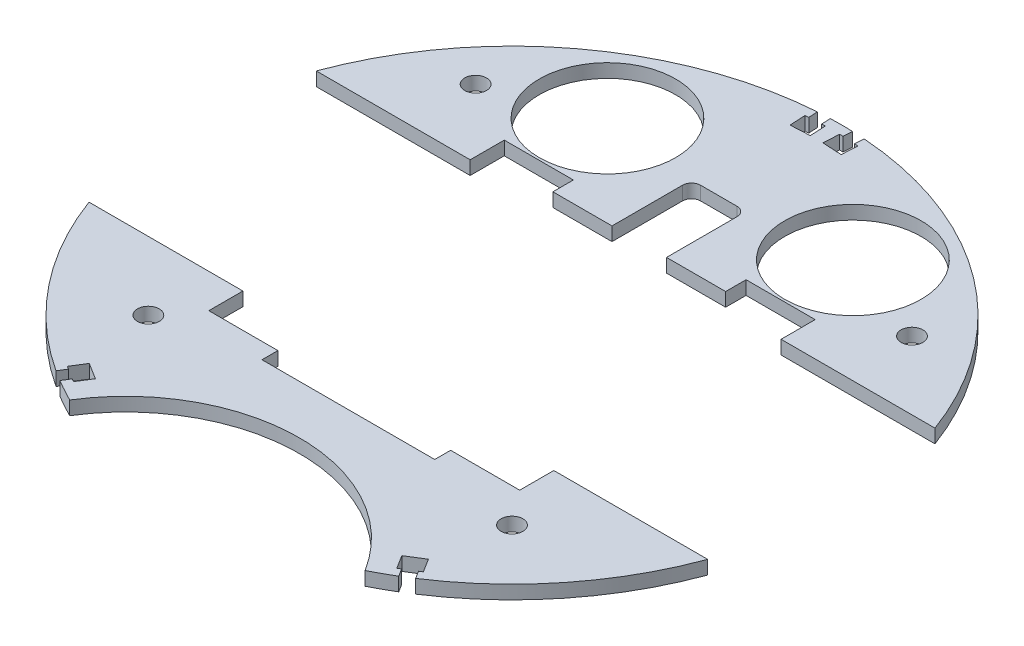
SolidWorks part; units mm, degrees
material "Acrylic (Medium-high impact)"
ref_plane "Front Plane" through (0, 0, 0) normal (0, 0, 1) x (1, 0, 0)
ref_plane "Top Plane" through (0, 0, 0) normal (0, 1, 0) x (1, 0, 0)
ref_plane "Right Plane" through (0, 0, 0) normal (1, 0, 0) x (0, 0, -1)
sketch "Sketch1" plane through (0, 0, 0) normal (0, 1, 0) x (1, 0, 0)
  line L0 (0, -85) -> (-32.4891, -64.8129) construction
  line L1 (0, -85) -> (0, 0) construction
  arc A0 (32.4891, -64.8129) -> (-32.4891, -64.8129) centre (0, 0) ccw
  arc A1 (32.4891, -64.8129) -> (-32.4891, -64.8129) centre (0, -85) ccw
  dimension "D1" = 145
  dimension "D2" = 76.5
  dimension "D3" = 85
extrude "Boss-Extrude1" add sketch "Sketch1" along normal blind 3
sketch "solenoid placement" plane through (0, 3, 0) normal (0, 1, 0) x (1, 0, 0)
  line L4 (-19, -36) -> (19, -36)
  line L5 (-19, 28) -> (-19, -36)
  line L10 (19, 28) -> (-19, 28)
  line L11 (19, -36) -> (19, 28)
  line L12 (-19, -36) -> (19, -36)
  line L13 (-19, 28) -> (-19, -36)
  line L14 (19, 28) -> (-19, 28)
  line L15 (19, -36) -> (19, 28)
  dimension "D1" = 0
extrude "Cut-Extrude1" cut sketch "solenoid placement" against normal through all
sketch "Sketch7" plane through (0, 3, 0) normal (0, 1, 0) x (1, 0, 0)
  circle A3 centre (27, 48) radius 15
  circle A4 centre (27, 48) radius 15
  circle A5 centre (-27, 48) radius 15
  circle A6 centre (-27, 48) radius 15
  dimension "D1" = 0
  dimension "D2" = 0
extrude "Cut-Extrude6" cut sketch "Sketch7" against normal through all
sketch "Sketch8" plane through (0, 3, 0) normal (0, 1, 0) x (1, 0, 0)
  circle A1 centre (40, -40) radius 2.4
  circle A2 centre (40, -40) radius 2.4
  circle A3 centre (-40, -40) radius 2.4
  circle A4 centre (-40, -40) radius 2.4
  circle A5 centre (48, 40) radius 2.4
  circle A6 centre (48, 40) radius 2.4
  circle A7 centre (-48, 40) radius 2.4
  circle A8 centre (-48, 40) radius 2.4
  dimension "D1" = 0
  dimension "D2" = 0
  dimension "D3" = 0
  dimension "D4" = 0
extrude "Cut-Extrude7" cut sketch "Sketch8" against normal through all
sketch "Sketch3" plane through (0, 3, 0) normal (0, 1, 0) x (1, 0, 0)
  line L1 (-34.2, -32.5007) -> (-22.2, -32.5007)
  line L2 (-34.2, 24.9993) -> (-68.0535, 24.9993)
  line L3 (-34.2, 32.4993) -> (-22.2, 32.4993)
  line L4 (-22.2, -32.5007) -> (-22.2, 32.4993) construction
  line L8 (0, 0) -> (0, 72.5) construction
  line L17 (-34.2, -32.5007) -> (-34.2, -25.0007)
  line L18 (-34.2, -25.0007) -> (-68.053, -25.0007)
  line L19 (-34.2, 24.9993) -> (-34.2, 32.4993)
  line L21 (-22.2, 32.4993) -> (-19, 32.4993)
  line L22 (-22.2, 32.4993) -> (-22.2, -32.5007) construction
  line L23 (-22.2, -32.5007) -> (-19, -32.5007)
  line L24 (-19, 32.4993) -> (-19, -32.5007)
  line L25 (22.2, 32.4993) -> (22.2, -32.5007) construction
  line L26 (22.2, -32.5007) -> (22.2, 32.4993) construction
  line L27 (19, 32.4993) -> (19, -32.5007)
  line L28 (22.2, -32.5007) -> (19, -32.5007)
  line L29 (22.2, 32.4993) -> (19, 32.4993)
  line L30 (34.2, 24.9993) -> (34.2, 32.4993)
  line L31 (34.2, -25.0007) -> (68.053, -25.0007)
  line L32 (34.2, -32.5007) -> (34.2, -25.0007)
  line L33 (34.2, 32.4993) -> (22.2, 32.4993)
  line L34 (34.2, 24.9993) -> (68.0535, 24.9993)
  line L35 (34.2, -32.5007) -> (22.2, -32.5007)
  line L36 (-19, 28) -> (-19, -36) construction
  arc A0 (32.4891, -64.8129) -> (-32.4891, -64.8129) centre (0, 0) ccw construction
  arc A2 (68.0535, 24.9993) -> (68.053, -25.0007) centre (0, 0) cw
  arc A3 (-68.0535, 24.9993) -> (-68.053, -25.0007) centre (0, 0) ccw
  point P31 (-34.2, -32.5007)
  dimension "D1" = 50
extrude "Cut-Extrude3" cut sketch "Sketch3" against normal through all
sketch "Sketch9" plane through (0, 3, 0) normal (0, 1, 0) x (1, 0, 0)
  line L0 (6, 43.5) -> (6, 28)
  line L1 (-6, 43.5) -> (-6, 28)
  line L2 (19, 28) -> (-19, 28) construction
  line L8 (-6, 28) -> (6, 28)
  line L10 (4, 45.5) -> (-4, 45.5)
  arc A0 (-6, 43.5) -> (-4, 45.5) centre (-4, 43.5) cw
  arc A1 (6, 43.5) -> (4, 45.5) centre (4, 43.5) ccw
  point P5 (0, 28)
  point P6 (0, 28)
  point P16 (-6, 45.5)
  point P19 (6, 45.5)
  dimension "D3" = 2
  dimension "D2" = 12
  dimension "D1" = 17.5
extrude "Cut-Extrude8" cut sketch "Sketch9" against normal through all
sketch "Sketch10" plane through (0, 3, 0) normal (0, 1, 0) x (1, 0, 0)
  line L0 (0, 0) -> (0, 72.5) construction
  line L1 (0, 0) -> (3.7944, 72.4006) construction
  line L2 (1.3844, 67.0194) -> (5.6286, 66.797)
  line L3 (1.3844, 67.0194) -> (1.5676, 70.5146)
  line L4 (5.6286, 66.797) -> (5.8118, 70.2922)
  line L5 (1.5676, 70.5146) -> (2.3415, 70.474)
  line L6 (2.3415, 70.474) -> (2.4462, 72.4713)
  line L7 (2.4462, 72.4713) -> (5.1425, 72.33)
  line L8 (5.1425, 72.33) -> (5.0378, 70.3327)
  line L9 (5.0378, 70.3327) -> (5.8118, 70.2922)
  line L10 (-5.0378, 70.3327) -> (-5.8118, 70.2922)
  line L11 (-5.1425, 72.33) -> (-5.0378, 70.3327)
  line L12 (-2.4462, 72.4713) -> (-5.1425, 72.33)
  line L13 (-2.3415, 70.474) -> (-2.4462, 72.4713)
  line L14 (-1.5676, 70.5146) -> (-2.3415, 70.474)
  line L15 (-5.6286, 66.797) -> (-5.8118, 70.2922)
  line L16 (-1.3844, 67.0194) -> (-1.5676, 70.5146)
  line L17 (-1.3844, 67.0194) -> (-5.6286, 66.797)
  line L18 (37.3067, -55.6931) -> (33.7025, -57.9453)
  line L19 (37.3067, -55.6931) -> (39.1614, -58.6613)
  line L20 (33.7025, -57.9453) -> (35.5572, -60.9135)
  line L21 (39.1614, -58.6613) -> (38.5042, -59.072)
  line L22 (38.5042, -59.072) -> (39.564, -60.7681)
  line L23 (39.564, -60.7681) -> (37.2743, -62.1989)
  line L24 (37.2743, -62.1989) -> (36.2144, -60.5028)
  line L25 (36.2144, -60.5028) -> (35.5572, -60.9135)
  line L26 (0, 0) -> (38.4191, -61.4835) construction
  line L27 (0, 0) -> (0, -85) construction
  line L28 (-33.7025, -57.9453) -> (-37.3067, -55.6931)
  line L29 (-33.7025, -57.9453) -> (-35.5572, -60.9135)
  line L30 (-37.3067, -55.6931) -> (-39.1614, -58.6613)
  line L31 (-35.5572, -60.9135) -> (-36.2144, -60.5028)
  line L32 (-36.2144, -60.5028) -> (-37.2743, -62.1989)
  line L33 (-37.2743, -62.1989) -> (-39.564, -60.7681)
  line L34 (-39.564, -60.7681) -> (-38.5042, -59.072)
  line L35 (-38.5042, -59.072) -> (-39.1614, -58.6613)
  line L36 (0, 0) -> (-38.4191, -61.4835) construction
  arc A1 (68.0535, 24.9993) -> (-68.0535, 24.9993) centre (0, 0) ccw construction
  point P1 (3.5065, 66.9082)
  point P15 (3.7944, 72.4006)
  point P36 (0, 0)
  point P49 (0, 0)
  dimension "D1" = 3.5
  dimension "D2" = 4.25
  dimension "D3" = 3
  dimension "D4" = 2.7
  dimension "D5" = 2
  dimension "D7" = 32
  dimension "D9" = 32
  dimension "D6" = 2
  dimension "D8" = 2
extrude "Cut-Extrude9" cut sketch "Sketch10" against normal through all
sketch "Sketch11" plane through (0, 3, 0) normal (0, 1, 0) x (1, 0, 0)
  line L4 (4, 48.5) -> (-4, 48.5)
  line L5 (7.1569, 48.5) -> (-7.1569, 48.5)
  line L10 (-8.4675, 63.6441) -> (-1.2274, 64.0235)
  line L11 (-8.8077, 70.1352) -> (-8.4675, 63.6441)
  line L12 (-6.4702, 63.7487) -> (-0.1047, 64.0823)
  line L13 (-8.6309, 66.7627) -> (-8.5721, 65.6413)
  line L17 (8.4675, 63.6441) -> (8.8077, 70.1352)
  line L18 (1.2274, 64.0235) -> (8.4675, 63.6441)
  line L19 (8.5721, 65.6413) -> (8.6309, 66.7627)
  line L20 (0.1047, 64.0823) -> (6.4702, 63.7487)
  arc A0 (-9.1412, 50.25) -> (-7.1569, 48.5) centre (-7.1569, 50.5) ccw
  arc A1 (9.1412, 50.25) -> (7.1569, 48.5) centre (7.1569, 50.5) cw
  arc A2 (18.004, 63.5907) -> (17.5082, 67.2585) centre (17.0044, 65.323) ccw
  arc A3 (10.9431, 68.6331) -> (8.6309, 66.7627) centre (10.6282, 66.658) ccw
  arc A4 (8.5721, 65.6413) -> (6.4702, 63.7487) centre (6.5749, 65.746) cw
  arc A5 (-0.1047, 64.0823) -> (0.1047, 64.0823) centre (0, 62.0851) cw
  arc A6 (-6.4702, 63.7487) -> (-8.5721, 65.6413) centre (-6.5749, 65.746) cw
  arc A7 (-10.9431, 68.6331) -> (-8.6309, 66.7627) centre (-10.6282, 66.658) cw
  arc A8 (-17.5082, 67.2585) -> (-18.004, 63.5907) centre (-17.0044, 65.323) ccw
  circle A9 centre (-27, 48) radius 18
  arc A10 (-9.1412, 50.25) -> (-18.004, 63.5907) centre (-27, 48) ccw
  circle A12 centre (27, 48) radius 18
  arc A13 (18.004, 63.5907) -> (9.1412, 50.25) centre (27, 48) ccw
  arc A15 (-4.9291, 69.325) -> (-65.2375, 23.9649) centre (0, 0) ccw
  arc A16 (-10.9431, 68.6331) -> (-17.5082, 67.2585) centre (0, 0) ccw
  arc A17 (17.5082, 67.2585) -> (10.9431, 68.6331) centre (0, 0) ccw
  dimension "D5" = 2
  dimension "D1" = 3
  dimension "D2" = 3
  dimension "D3" = 3
  dimension "D4" = 3
  dimension "D6" = 3
  dimension "D7" = 3
extrude "Cut-Extrude10" [suppressed] cut sketch "Sketch11" against normal through all
equation "\"smallPulleyTeeth\"= 30"
equation "\"largePulleyTeeth\"= 30"
equation "\"eighthThick\"= 3.0mm"
equation "\"sixteenthThick\" = 1.7mm"
equation "\"quarterThick\"=6.0mm"
equation "\"OD\" = 145mm"
equation "\"puckAngle\" = 60.5deg"
equation "\"D1@Sketch1\"=\"OD\""
equation "\"puckDiam\" = 76.5mm"
equation "\"D2@Sketch1\"=\"puckDiam\""
equation "\"D1@Boss-Extrude1\"=\"eighthThick\""
equation "\"axlePress\" = 5.9mm"
equation "\"press\" = 0.2mm"
equation "\"wheelClear\" = 0.3mm"
equation "\"10-32clear\" = 4.8mm"
equation "\"6-32clear\" = 3.3mm"
equation "\"8-32clear\" = 4.0mm"
equation "\"4-40clear\" = 3.0mm"
equation "\"wheelHeight\" = 22mm"
equation "\"wheelWell\" = 65mm"
equation "\"puckDist\" = 85mm"
equation "\"D3@Sketch1\"=\"puckDist\""
equation "\"scoopFillet\" = 5mm"
equation "\"10-32tap\" = 4.45mm"
equation "\"ledSmall\" = 3.1mm"
equation "\"ledLarge\" = 4.2mm"
equation "\"ledLength\" = 4.2mm"
equation "\"4-40close\" = 2.7mm"
equation "\"4-40nutThick\" = 2.2mm"
equation "\"4-40nutWidth\" = 6.2mm"
equation "\"4-40insertHeight\" = 3.5mm"
equation "\"4-40insert\" = 4.25mm"
equation "\"D1@Sketch10\"=\"4-40insertHeight\""
equation "\"D2@Sketch10\"=\"4-40insert\""
equation "\"D4@Sketch10\"=\"4-40close\""
